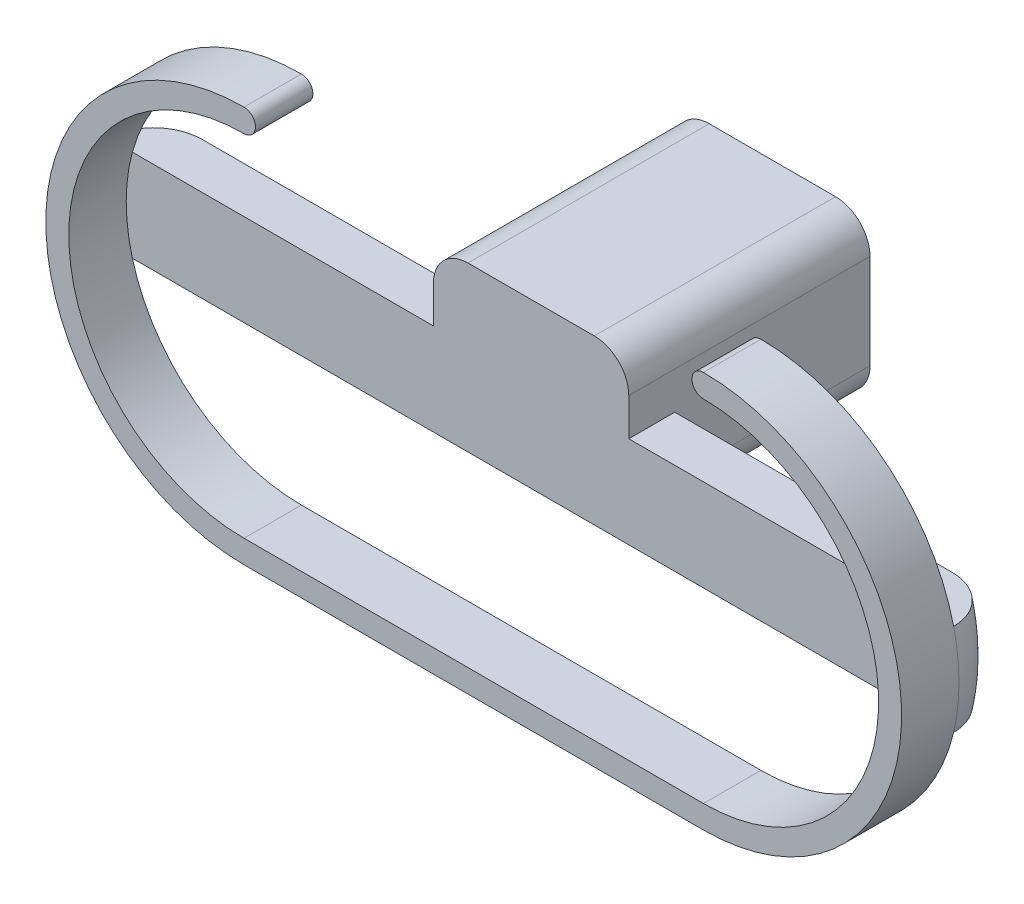
SolidWorks part; units mm, degrees
ref_plane "Front Plane" through (0, 0, 0) normal (0, 0, 1) x (1, 0, 0)
ref_plane "Top Plane" through (0, 0, 0) normal (0, 1, 0) x (1, 0, 0)
ref_plane "Right Plane" through (0, 0, 0) normal (1, 0, 0) x (0, 0, -1)
sketch "Sketch3" plane through (0, 0, 0) normal (0, 0, 1) x (1, 0, 0)
  line L0 (-20, 0) -> (20, 0) construction
  line L1 (-20, -17.25) -> (20, -17.25)
  line L2 (-20, -15.25) -> (20, -15.25)
  arc A0 (-20, 15.25) -> (-20, -15.25) centre (-20, 0) ccw
  arc A1 (20, -15.25) -> (20, 15.25) centre (20, 0) ccw
  arc A2 (-20, 15.25) -> (-20, 17.25) centre (-20, 16.25) ccw
  arc A3 (20, 15.25) -> (20, 17.25) centre (20, 16.25) cw
  arc A4 (-20, 17.25) -> (-20, -17.25) centre (-20, 0) ccw
  arc A5 (20, 17.25) -> (20, -17.25) centre (20, 0) cw
  point P3 (0, 0)
  point P15 (-35.25, 0)
  point P16 (35.25, 0)
  point P17 (0, -15.25)
  dimension "D3" = 1
  dimension "D4" = 1
  dimension "D5" = 17.25
  dimension "D1" = 70.5
  dimension "D2" = 30.5
extrude "Boss-Extrude1" add sketch "Sketch3" along normal blind 5
sketch "Sketch4" plane through (0, 0, 0) normal (0, 0, -1) x (-1, 0, 0)
  line L0 (0, 0) -> (-29.0824, 0) construction
  line L1 (-36.7798, 4) -> (36.7798, 4)
  line L2 (-36.7798, -4) -> (36.7798, -4)
  arc A8 (-36.7798, 4) -> (-36.7798, -4) centre (-20, 0) ccw
  arc A9 (36.7798, 4) -> (36.7798, -4) centre (22.0638, 0) cw
  arc A10 (-20, 17.25) -> (-20, -17.25) centre (-20, 0) ccw construction
  point P6 (0, 4)
  point P9 (0, -4)
  point P11 (0, 0)
  point P12 (-37.1337, 2)
  dimension "D3" = 15.25
  dimension "D4" = 17.25
  dimension "D1" = 4
  dimension "D2" = 4
extrude "Boss-Extrude2" add sketch "Sketch4" along normal blind 4
fillet "Fillet1" radius 4 2 edges at (-37.3138, 0, -4) (37.25, 0, -4)
sketch "Sketch5" plane through (0, 4, 0) normal (0, 1, 0) x (1, 0, 0)
  line L0 (-34.7161, 0) -> (34.7161, 0) construction
  line L1 (-8.5, 0) -> (8.5, 0)
  line L2 (-8.5, 0) -> (-8.5, 4)
  line L3 (-8.5, 4) -> (8.5, 4)
  line L4 (8.5, 0) -> (8.5, 4)
  line L5 (-32.5786, 4) -> (32.6318, 4) construction
  point P8 (0, 0)
  dimension "D1" = 17
extrude "Boss-Extrude3" add sketch "Sketch5" along normal blind 6.25
sketch "Sketch6" plane through (0, 0, -4) normal (0, 0, -1) x (-1, 0, 0)
  line L0 (-8.5, 7.125) -> (8.5, 7.125) construction
  line L1 (-8.5, 10.25) -> (-8.5, 4) construction
  line L2 (8.5, 10.25) -> (8.5, 4) construction
  circle A0 centre (-5.5, 7.125) radius 1.5
  circle A1 centre (5.5, 7.125) radius 1.5
  point P10 (0, 0)
  point P11 (-5.6944, 7.125)
  point P12 (0, 7.125)
  dimension "D3" = 3
  dimension "D4" = 3
  dimension "D1" = 5.5
  dimension "D2" = 5.5
sketch "Sketch8" plane through (0, 0, -4) normal (0, 0, -1) x (-1, 0, 0)
  line L0 (-32.6318, -4) -> (32.5786, -4) construction
  line L1 (-8.5, 10.25) -> (8.5, 10.25)
  line L2 (-8.5, 10.25) -> (-8.5, -4)
  line L3 (-8.5, -4) -> (8.5, -4)
  line L4 (8.5, 10.25) -> (8.5, -4)
  point P7 (0, 0)
  point P8 (0, 0)
extrude "Boss-Extrude4" add sketch "Sketch8" along normal blind 17
extrude "Cut-Extrude1" cut sketch "Sketch6" along normal through all
fillet "Fillet3" radius 3 4 edges at (-8.5, -4, -12.5) (8.5, -4, -12.5) (-8.5, 10.25, -10.5) (8.5, 10.25, -10.5)
